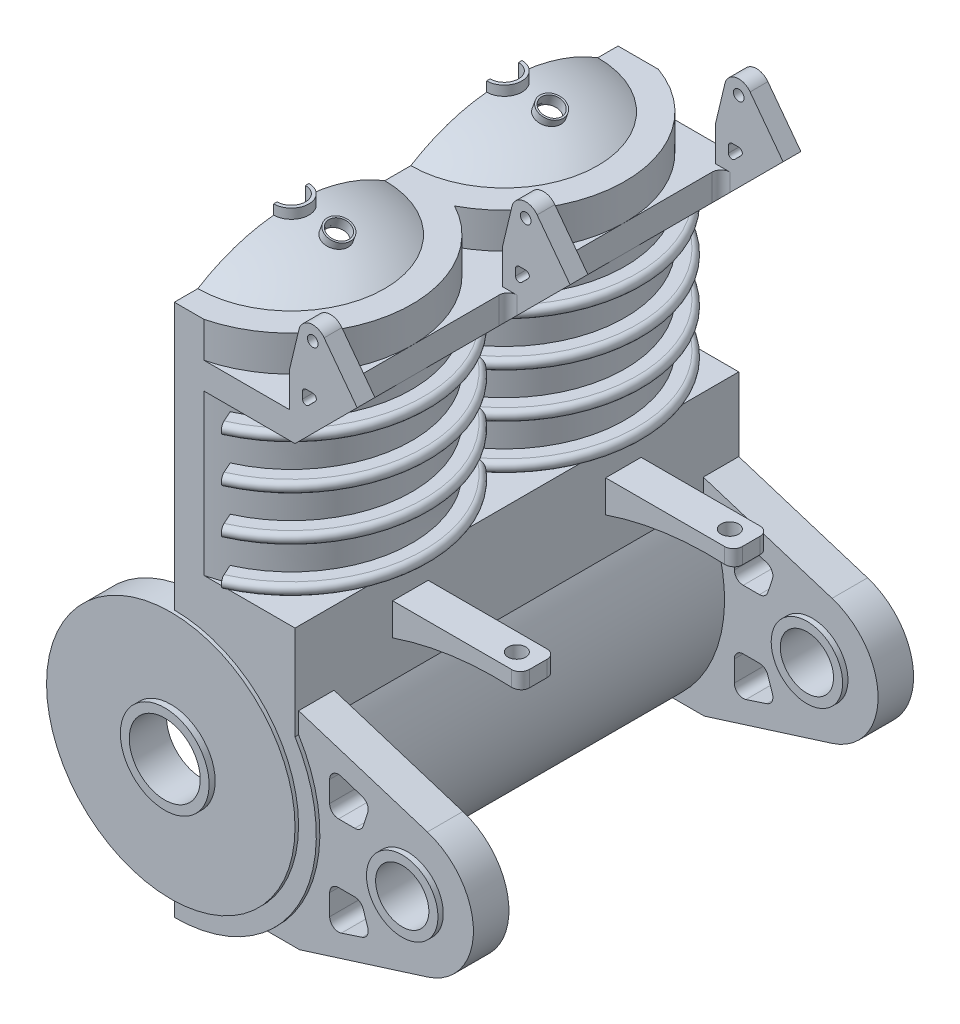
SolidWorks part; units mm, degrees
ref_plane "Front Plane" through (0, 0, 0) normal (0, 0, 1) x (1, 0, 0)
ref_plane "Top Plane" through (0, 0, 0) normal (0, 1, 0) x (1, 0, 0)
ref_plane "Right Plane" through (0, 0, 0) normal (1, 0, 0) x (0, 0, -1)
sketch "Sketch1" plane through (0, 0, 0) normal (0, 0, 1) x (1, 0, 0)
  line L0 (0, 0) -> (0, 28.02)
  line L1 (0, 28.02) -> (6.8, 28.02)
  line L2 (6.8, 28.02) -> (6.8, 12.2143)
  arc A0 (6.8, 12.2143) -> (0, 0) centre (0, 8) cw
  dimension "D3" = 8
  dimension "D1" = 28.02
  dimension "D2" = 6.8
extrude "Boss-Extrude1" add sketch "Sketch1" along normal blind 25
sketch "Sketch2" plane through (0, 28.02, 0) normal (0, 1, 0) x (1, 0, 0)
  line L0 (0, -25) -> (0, 0) construction
  line L1 (6.8, -25) -> (0, -25) construction
  circle A0 centre (0, -6.41) radius 5
  circle A1 centre (0, -18.41) radius 5
  dimension "D1" = 10
  dimension "D2" = 12
  dimension "D3" = 6.59
extrude "Cut-Extrude1" cut sketch "Sketch2" against normal blind 20
sketch "Sketch3" plane through (0, 0, 25) normal (0, 0, 1) x (1, 0, 0)
  circle A0 centre (0, 8) radius 7
  dimension "D1" = 14
extrude "Cut-Extrude2" cut sketch "Sketch3" against normal through all
ref_plane "Plane1" through (0, 26.52, 0) normal (0, 1, 0) x (1, 0, 0)
sketch "Sketch4" plane through (0, 26.52, 0) normal (0, 1, 0) x (1, 0, 0)
  line L6 (0, 0.39) -> (11.8677, 0.39)
  line L7 (11.8677, 0.39) -> (11.8677, -25.21)
  line L8 (11.8677, -25.21) -> (0, -25.21)
  arc A15 (0, -13.21) -> (0, 0.39) centre (0, -6.41) ccw
  arc A16 (3.2, -12.41) -> (0, 0.39) centre (0, -6.41) ccw
  arc A18 (0, -25.21) -> (0, -11.61) centre (0, -18.41) ccw
  arc A19 (0, -25.21) -> (3.2, -12.41) centre (0, -18.41) ccw
  dimension "D1" = 1.8
  dimension "D2" = 1.8
extrude "Cut-Extrude3" cut sketch "Sketch4" against normal blind 9
sketch "Sketch6" plane through (0, 0, 0) normal (-1, 0, 0) x (0, 0, 1)
  line L0 (6.41, 28.02) -> (6.41, -2.6597) construction
  line L1 (0.17, 27.17) -> (0.68, 27.17)
  line L2 (0.17, 27.17) -> (0.17, 17.17)
  line L3 (0.17, 17.17) -> (0.68, 17.17)
  line L4 (0.68, 27.17) -> (0.68, 17.17)
  line L5 (1.41, 28.02) -> (0, 28.02) construction
  line L6 (0, 28.02) -> (0, 15) construction
  line L7 (0.17, 25.87) -> (-1.07, 25.87)
  line L8 (0.17, 25.87) -> (0.17, 25.27)
  line L9 (0.17, 25.27) -> (-1.07, 25.27)
  line L11 (0.17, 23.37) -> (-1.07, 23.37)
  line L12 (0.17, 23.37) -> (0.17, 22.77)
  line L13 (0.17, 22.77) -> (-1.07, 22.77)
  line L15 (0.17, 20.87) -> (-1.07, 20.87)
  line L16 (0.17, 20.87) -> (0.17, 20.27)
  line L17 (0.17, 20.27) -> (-1.07, 20.27)
  line L19 (0.17, 18.37) -> (-1.07, 18.37)
  line L20 (0.17, 18.37) -> (0.17, 17.77)
  line L21 (0.17, 17.77) -> (-1.07, 17.77)
  line L22 (11.41, 28.02) -> (1.41, 28.02) construction
  arc A0 (-1.07, 25.87) -> (-1.07, 25.27) centre (-1.07, 25.57) ccw
  arc A1 (-1.07, 23.37) -> (-1.07, 22.77) centre (-1.07, 23.07) ccw
  arc A2 (-1.07, 20.87) -> (-1.07, 20.27) centre (-1.07, 20.57) ccw
  arc A3 (-1.07, 18.37) -> (-1.07, 17.77) centre (-1.07, 18.07) ccw
  dimension "D13" = 0.3
  dimension "D1" = 0.51
  dimension "D2" = 10
  dimension "D3" = 0.68
  dimension "D4" = 0.85
  dimension "D5" = 0.6
  dimension "D6" = 0.6
  dimension "D7" = 2.15
  dimension "D8" = 2.5
  dimension "D9" = 2.5
  dimension "D10" = 2.5
  dimension "D11" = 1.75
  dimension "D12" = 0.6
  dimension "D14" = 1.75
  dimension "D15" = 1.75
revolve "Revolve1" add sketch "Sketch6" angle 156 about L0
pattern_linear "LPattern1" count 2 spacing 12 along (0, 0, 1) of "Revolve1"
sketch "Sketch7" plane through (0, 28.02, 0) normal (0, 1, 0) x (1, 0, 0)
  circle A0 centre (0, -6.41) radius 5
  dimension "D1" = 10
extrude "Cut-Extrude4" cut sketch "Sketch7" against normal blind 15 contours A0
sketch "Sketch8" plane through (0, 0, 0) normal (0, 0, -1) x (-1, 0, 0)
  circle A0 centre (0, 8) radius 7
  circle A1 centre (0, 8) radius 2.5
  dimension "D1" = 14
  dimension "D2" = 5
extrude "Boss-Extrude2" add sketch "Sketch8" along normal blind 0.5 and the other way blind 1
pattern_linear "LPattern2" count 3 spacing 12 along (0, 0, 1) of "Boss-Extrude2"
sketch "Sketch9" plane through (0, 0, 25) normal (0, 0, 1) x (1, 0, 0)
  circle A0 centre (0, 8) radius 2.5 construction
  circle A1 centre (0, 8) radius 2.5
  arc A4 (0, 1) -> (0, 15) centre (0, 8) ccw
  arc A5 (0, 15) -> (0, 1) centre (0, 8) ccw
  arc A6 (0, 1) -> (0, 15) centre (0, 8) ccw
  arc A7 (0, 15) -> (0, 1) centre (0, 8) ccw
  dimension "D1" = 0
extrude "Boss-Extrude3" add sketch "Sketch9" along normal blind 0.2
sketch "Sketch11" plane through (0, 0, -0.5) normal (0, 0, -1) x (-1, 0, 0)
  circle A0 centre (0, 8) radius 2.5
  circle A1 centre (0, 8) radius 2
  dimension "D1" = 5
  dimension "D2" = 4
extrude "Boss-Extrude4" add sketch "Sketch11" along normal blind 0.5 and the other way blind 1.6
pattern_linear "LPattern3" count 3 spacing 12.22 along (0, 0, 1) of "Boss-Extrude4"
sketch "Sketch12" plane through (0, 28.02, 0) normal (0, 1, 0) x (1, 0, 0)
  line L0 (0, -13.41) -> (0, -11.41) construction
  line L1 (0, -13.41) -> (0, -11.41)
  line L2 (0, -23.41) -> (0, -25)
  line L3 (0, -25) -> (1.6769, -25)
  line L4 (0, -1.41) -> (0, 0)
  line L5 (0, 0) -> (2.2698, 0)
  arc A0 (0, -11.41) -> (0, -1.41) centre (0, -6.41) ccw construction
  arc A1 (0, -23.41) -> (0, -13.41) centre (0, -18.41) ccw construction
  arc A2 (3.2, -12.41) -> (6.8, -6.41) centre (0, -6.41) ccw construction
  arc A3 (6.8, -6.41) -> (2.2698, 0) centre (0, -6.41) ccw construction
  arc A4 (6.8, -6.41) -> (2.2698, 0) centre (0, -6.41) ccw
  arc A5 (3.2, -12.41) -> (6.8, -6.41) centre (0, -6.41) ccw
  arc A6 (0, -23.41) -> (0, -13.41) centre (0, -18.41) ccw
  arc A7 (0, -11.41) -> (0, -1.41) centre (0, -6.41) ccw
  arc A8 (1.6769, -25) -> (6.8, -18.41) centre (0, -18.41) ccw construction
  arc A9 (6.8, -18.41) -> (3.2, -12.41) centre (0, -18.41) ccw construction
  arc A10 (1.6769, -25) -> (6.8, -18.41) centre (0, -18.41) ccw
  arc A11 (6.8, -18.41) -> (3.2, -12.41) centre (0, -18.41) ccw
extrude "Boss-Extrude5" add sketch "Sketch12" along normal blind 2
sketch "Sketch13" plane through (0, 0, 0) normal (0, 0, -1) x (-1, 0, 0)
  line L0 (0, 8) -> (-12.94, 8) construction
  line L1 (-2.0551, 7.56) -> (-12.94, 7.56) construction
  line L2 (-6.8, 13.386) -> (-14.0556, 11.0983)
  line L3 (-6.8, 12.2143) -> (-6.8, 17.52) construction
  line L4 (-14.0556, 4.0217) -> (-6.8557, 1.7516)
  line L5 (-6.8557, 1.7516) -> (-4.9957, 1.7516)
  line L6 (-6.8, 12.2143) -> (-6.8, 13.386)
  circle A0 centre (-12.94, 7.56) radius 2.013
  arc A1 (-14.0556, 11.0983) -> (-14.0556, 4.0217) centre (-12.94, 7.56) ccw
  arc A2 (-6.8, 12.2143) -> (0, 0) centre (0, 8) ccw construction
  arc A3 (-6.8, 12.2143) -> (0, 0) centre (0, 8) ccw
  line M11 (-6.8, 17.52) -> (-6.8, 12.2143)
  arc M12 (-6.8, 12.2143) -> (0, 0) centre (0, 8) ccw
  dimension "D3" = 4.026
  dimension "D4" = 3.71
  dimension "D1" = 0.44
  dimension "D2" = 12.94
  dimension "D5" = 35
  dimension "D6" = 1.86
extrude "Boss-Extrude6" add sketch "Sketch13" against normal blind 2 contours L2 A1 L4 L5 A0 M12 M11 region at (10.8383, 7.3802, 0)
pattern_linear "LPattern4" count 2 spacing 22.8 along (0, 0, 1) of "Boss-Extrude6"
sketch "Sketch14" plane through (0, 0, 0) normal (0, 0, -1) x (-1, 0, 0)
  circle A0 centre (-12.94, 7.56) radius 2.013 construction
  circle A1 centre (-12.94, 7.56) radius 2.013
  circle A2 centre (-12.94, 7.56) radius 1.5
  dimension "D1" = 3
extrude "Boss-Extrude7" add sketch "Sketch14" along normal blind 0.3 and the other way blind 2.3
pattern_linear "LPattern5" count 2 spacing 22.8 along (0, 0, 1) of "Boss-Extrude7"
sketch "Sketch15" plane through (0, 0, 0) normal (0, 0, -1) x (-1, 0, 0)
  line L0 (-9.2065, 11.3835) -> (-10.3784, 11)
  line L1 (-10.698, 10.3692) -> (-10.4393, 9.5787)
  line L2 (-9.9641, 9.2342) -> (-9.051, 9.2342)
  line L3 (-8.551, 9.7342) -> (-8.551, 10.9083)
  line L4 (-12.94, 7.56) -> (-7.5881, 7.56) construction
  line L5 (-8.551, 5.3858) -> (-8.551, 4.2117)
  line L6 (-9.9641, 5.8858) -> (-9.051, 5.8858)
  line L7 (-10.698, 4.7508) -> (-10.4393, 5.5413)
  line L8 (-9.2065, 3.7365) -> (-10.3784, 4.12)
  arc A0 (-9.051, 9.2342) -> (-8.551, 9.7342) centre (-9.051, 9.7342) ccw
  arc A1 (-10.4393, 9.5787) -> (-9.9641, 9.2342) centre (-9.9641, 9.7342) ccw
  arc A2 (-10.3784, 11) -> (-10.698, 10.3692) centre (-10.2228, 10.5248) ccw
  arc A3 (-9.2065, 11.3835) -> (-8.551, 10.9083) centre (-9.051, 10.9083) cw
  arc A4 (-9.2065, 3.7365) -> (-8.551, 4.2117) centre (-9.051, 4.2117) ccw
  arc A5 (-10.3784, 4.12) -> (-10.698, 4.7508) centre (-10.2228, 4.5952) cw
  arc A6 (-10.4393, 5.5413) -> (-9.9641, 5.8858) centre (-9.9641, 5.3858) cw
  arc A7 (-9.051, 5.8858) -> (-8.551, 5.3858) centre (-9.051, 5.3858) cw
  dimension "D1" = 0.5
  dimension "D2" = 0.5
extrude "Cut-Extrude5" cut sketch "Sketch15" against normal through all
sketch "Sketch16" plane through (0, 0, 0) normal (-1, 0, 0) x (0, 0, 1)
  line L0 (18.41, 30.02) -> (18.41, 21.52) construction
  line L1 (23.41, 30.02) -> (13.41, 30.02) construction
  line L2 (11.41, 30.02) -> (13.41, 30.02) construction
  line L3 (18.41, 31.52) -> (18.41, 31.4)
  line L4 (13.1422, 30.02) -> (13.3737, 30.02)
  arc A0 (13.1422, 30.02) -> (18.41, 31.52) centre (18.41, 21.52) cw
  arc A1 (13.3737, 30.02) -> (18.41, 31.4) centre (18.41, 21.52) cw
  arc A2 (13.2054, 29.918) -> (18.41, 31.4) centre (18.41, 21.52) cw construction
  dimension "D1" = 10
  dimension "D3" = 0.12
  dimension "D2" = 8.5
revolve "Revolve7" add sketch "Sketch16" angle 180 about L0 region at (0, 31.46, 18.3552)
pattern_linear "LPattern6" count 2 spacing 12 along (0, 0, -1) of "Revolve7"
sketch "Sketch17" plane through (0, 30.02, 0) normal (0, 1, 0) x (1, 0, 0)
  line L0 (0, -1.1422) -> (0, -11.6778) construction
  line L1 (0, -13.1422) -> (0, -23.6778) construction
  circle A0 centre (0, -6.41) radius 0.995
  circle A1 centre (0, -18.41) radius 0.995
  dimension "D1" = 1.99
  dimension "D2" = 1.99
extrude "Cut-Extrude6" cut sketch "Sketch17" along normal through all
sketch "Sketch18" plane through (0, 30.02, 0) normal (0, 1, 0) x (1, 0, 0)
  line L0 (0, -5.415) -> (0, -5.61)
  line L1 (0, -7.405) -> (0, -7.21)
  line L2 (0, -17.415) -> (0, -17.61)
  line L3 (0, -19.405) -> (0, -19.21)
  arc A0 (0, -19.405) -> (0, -17.415) centre (0, -18.41) ccw construction
  arc A1 (0, -19.405) -> (0, -17.415) centre (0, -18.41) ccw
  arc A2 (0, -7.405) -> (0, -5.415) centre (0, -6.41) ccw construction
  arc A3 (0, -7.405) -> (0, -5.415) centre (0, -6.41) ccw
  arc A4 (0, -7.21) -> (0, -5.61) centre (0, -6.41) ccw
  arc A5 (0, -19.21) -> (0, -17.61) centre (0, -18.41) ccw
  dimension "D1" = 1.6
  dimension "D2" = 1.6
extrude "Boss-Extrude8" add sketch "Sketch18" along normal blind 0.8 from offset 1.2
ref_plane "Plane2" through (9.6482, 26.5083, 0) normal (0.342, 0.9397, 0) x (0, 0, 1)
sketch "Sketch19" plane through (9.6482, 26.5083, 0) normal (0.342, 0.9397, 0) x (0, 0, 1)
  line L0 (6.41, -11.301) -> (6.41, -8.301) construction
  line L1 (6.41, -8.301) -> (18.2215, -8.301) construction
  line L2 (18.3967, -10.9515) -> (18.3967, -8.301) construction
  circle A0 centre (6.41, -8.301) radius 0.6
  circle A1 centre (18.3967, -8.301) radius 0.6
  dimension "D2" = 1.2
  dimension "D1" = 3
extrude "Cut-Extrude11" cut sketch "Sketch19" along normal through all
sketch "Sketch20" plane through (0, 0, 0) normal (0, 0, -1) x (-1, 0, 0)
  line L0 (-6.8, 26.52) -> (-6.5, 26.52)
  line L1 (-6.8, 26.52) -> (-2.2698, 26.52) construction
  line L2 (-6.5, 26.52) -> (-6.5, 30.02)
  line L3 (-2.2698, 30.02) -> (-6.8, 30.02) construction
  line L4 (-6.5, 30.02) -> (-8.82, 30.02)
  line L5 (-8.82, 30.02) -> (-9.9443, 31.1443)
  line L7 (-10.6416, 30.3616) -> (-6.8, 26.52)
  line L8 (-7.9417, 29.1417) -> (-7.5638, 28.7638)
  line L9 (-7.2224, 28.9052) -> (-7.2224, 29.2831)
  line L10 (-7.4224, 29.4831) -> (-7.8003, 29.4831)
  arc A0 (-9.9443, 31.1443) -> (-10.6416, 30.3616) centre (-10.3155, 30.7731) ccw
  circle A1 centre (-10.3155, 30.7731) radius 0.3
  arc A2 (-7.5638, 28.7638) -> (-7.2224, 28.9052) centre (-7.4224, 28.9052) ccw
  arc A3 (-7.9417, 29.1417) -> (-7.8003, 29.4831) centre (-7.8003, 29.2831) cw
  arc A4 (-7.2224, 29.2831) -> (-7.4224, 29.4831) centre (-7.4224, 29.2831) ccw
  dimension "D7" = 0.6
  dimension "D9" = 1.05
  dimension "D10" = 0.2
  dimension "D1" = 135
  dimension "D2" = 1.0465
  dimension "D3" = 2.32
  dimension "D4" = 0.3
  dimension "D5" = 1.59
  dimension "D6" = 1.0465
  dimension "D8" = 0.525
extrude "Boss-Extrude9" add sketch "Sketch20" against normal blind 1
pattern_linear "LPattern7" count 3 spacing 12 along (0, 0, 1) of "Boss-Extrude9"
fillet "Fillet1" radius 0.5 4 edges at (6.8, 27.27, 24) (6.8, 27.27, 1) (6.8, 27.27, 13) (6.8, 27.27, 12)
sketch "Sketch21" plane through (0, 0, 0) normal (0, 0, -1) x (-1, 0, 0)
  line L0 (-6.8, 16.1) -> (-14, 16.1)
  line L1 (-6.8, 13.386) -> (-6.8, 17.52) construction
  line L2 (-14, 16.1) -> (-14, 15.2)
  line L12 (-6.8, 17.52) -> (-6.8, 13.386)
  line L13 (-6.8, 13.386) -> (-14.0556, 11.0983)
  line L14 (-14.0556, 4.0217) -> (-6.8557, 1.7516)
  line L15 (-6.8557, 1.7516) -> (-4.9957, 1.7516)
  line L16 (0, 0) -> (0, 1)
  line L17 (0, 15) -> (0, 17.77)
  line L18 (0, 17.77) -> (-2.2698, 17.77)
  line L19 (-2.2698, 17.77) -> (-2.2698, 17.52)
  line L20 (-2.2698, 17.52) -> (-6.8, 17.52)
  line L21 (-6.8, 16.1) -> (-6.8, 14.2899)
  arc A0 (-14, 15.2) -> (-6.8, 14.2899) centre (-12.6045, -2.6957) cw
  arc A4 (-14.0556, 11.0983) -> (-14.0556, 4.0217) centre (-12.94, 7.56) ccw
  arc A5 (-4.9957, 1.7516) -> (0, 0) centre (0, 8) ccw
  arc A6 (0, 15) -> (0, 1) centre (0, 8) ccw
  point P7 (0, 8)
  dimension "D3" = 17.95
  dimension "D1" = 0.9
  dimension "D2" = 7.2
  dimension "D4" = 8.1
  dimension "D5" = 0
extrude "Boss-Extrude10" add sketch "Sketch21" against normal blind 2 from offset 5.5 offset against normal yes
pattern_linear "LPattern8" count 2 spacing 12 along (0, 0, 1) of "Boss-Extrude10"
sketch "Sketch22" plane through (0, 16.1, 0) normal (0, 1, 0) x (1, 0, 0)
  line L0 (14, -7.5) -> (14, -5.5) construction
  line L1 (14, -6.5) -> (12.8, -6.5) construction
  line L2 (14, -18.5) -> (12.8, -18.5) construction
  line L3 (14, -19.5) -> (14, -17.5) construction
  circle A0 centre (12.8, -6.5) radius 0.5
  circle A1 centre (12.8, -18.5) radius 0.5
  dimension "D1" = 1.2
  dimension "D2" = 1
  dimension "D3" = 1
  dimension "D4" = 1.2
extrude "Cut-Extrude12" cut sketch "Sketch22" against normal blind 2
fillet "Fillet2" radius 0.5 4 edges at (14, 15.65, 5.5) (14, 15.65, 7.5) (14, 15.65, 17.5) (14, 15.65, 19.5)
sketch "Sketch23" plane through (0, 0, 25) normal (0, 0, 1) x (1, 0, 0)
  line L1 (6.5, 30.02) -> (15.2867, 30.02)
  line L2 (6.5, 30.02) -> (6.5, 31.8396)
  line L3 (6.5, 31.8396) -> (15.2867, 31.8396)
  line L4 (15.2867, 30.02) -> (15.2867, 31.8396)
extrude "Cut-Extrude13" cut sketch "Sketch23" against normal through all
sketch "Sketch24" plane through (0, 0, 25) normal (0, 0, 1) x (1, 0, 0)
  line L0 (6.5, 30.02) -> (7.0219, 32.2058)
  line L1 (8.44, 32.5) -> (10.3, 30.02)
  line L2 (6.5, 30.02) -> (10.3, 30.02) construction
  line L3 (0, 30.02) -> (0, 15) construction
  arc A0 (7.0219, 32.2058) -> (8.44, 32.5) centre (7.8, 32.02) cw
  circle A1 centre (7.8, 32.02) radius 0.3
  line M4 (10.3, 30.02) -> (6.5, 30.02)
  dimension "D1" = 0.6
  dimension "D2" = 0.8
  dimension "D3" = 2
  dimension "D4" = 7.8
extrude "Boss-Extrude11" add sketch "Sketch24" against normal blind 1 contours A0 L0 L1 A1 M4 region at (8.1342, 31.0897, 25)
pattern_linear "LPattern9" count 3 spacing 12 along (0, 0, -1) of "Boss-Extrude11"
extrude "Extrude-Thin1" add sketch "Sketch19<2>" along normal blind 0.5 from offset 1.9 thin thin type one direction wall 0.1
sketch "Sketch19<2>" plane through (9.6482, 26.5083, 0) normal (0.342, 0.9397, 0) x (0, 0, 1) same geometry as "Sketch19"
